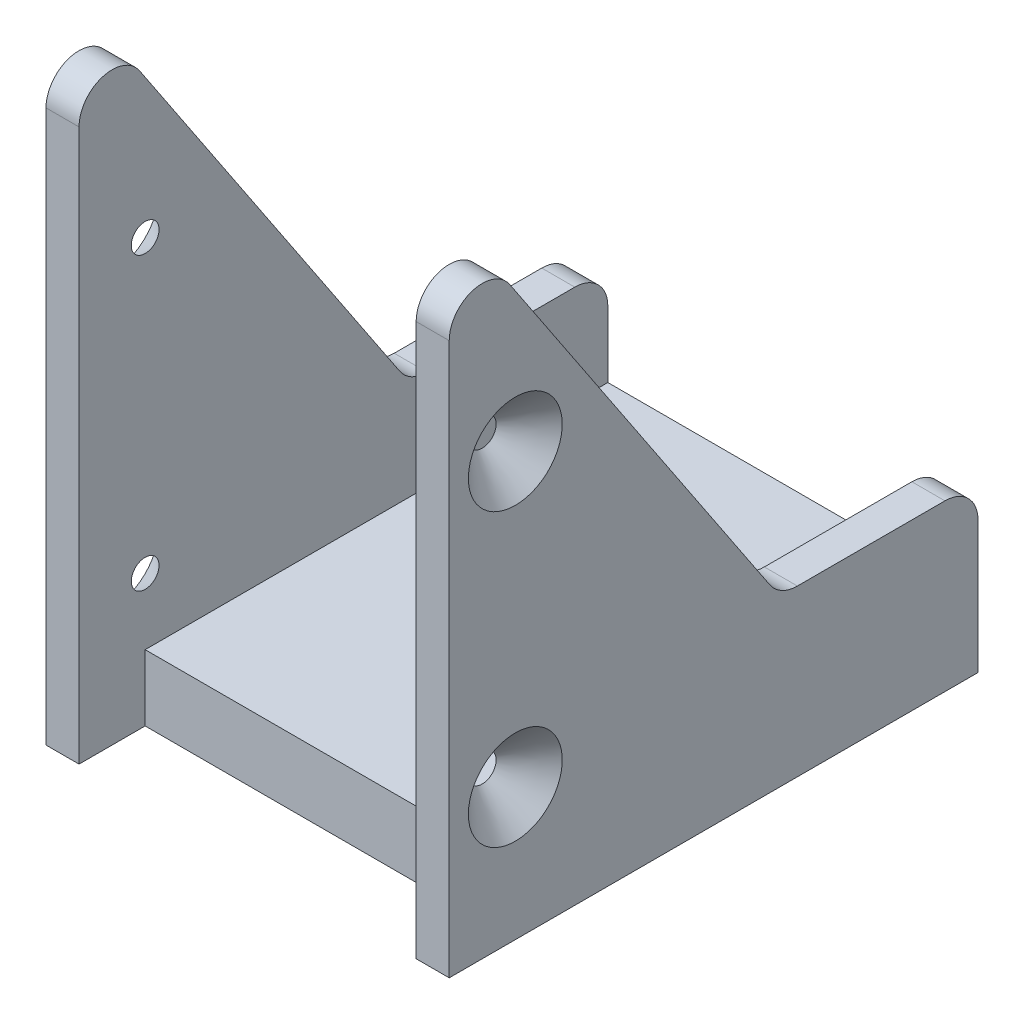
SolidWorks part; units mm, degrees
material "ABS"
ref_plane "Front Plane" through (0, 0, 0) normal (0, 0, 1) x (1, 0, 0)
ref_plane "Top Plane" through (0, 0, 0) normal (0, 1, 0) x (1, 0, 0)
ref_plane "Right Plane" through (0, 0, 0) normal (1, 0, 0) x (0, 0, -1)
sketch "Sketch1" plane through (0, 0, 0) normal (0, 0, 1) x (1, 0, 0)
  line L1 (-30.5, 50) -> (30.5, 50)
  line L2 (-30.5, 50) -> (-30.5, -50)
  line L3 (-30.5, -50) -> (30.5, -50)
  line L4 (30.5, 50) -> (30.5, -50)
  line L5 (-30.5, 50) -> (30.5, -50) construction
  line L6 (-30.5, -50) -> (30.5, 50) construction
  point P0 (0, 0)
  dimension "D1" = 61
  dimension "D2" = 100
extrude "Boss-Extrude1" add sketch "Sketch1" against normal blind 80
sketch "Sketch2" plane through (-30.5, 0, 0) normal (-1, 0, 0) x (0, 0, 1)
  line L0 (-80, -25) -> (-50, -25)
  line L1 (-80, 50) -> (-80, -50) construction
  line L2 (-50, -25) -> (0, 50)
  line L3 (-80, -25) -> (-80, -50)
  line L4 (-80, -50) -> (0, -50)
  line L5 (0, -50) -> (0, 50)
  dimension "D1" = 30
  dimension "D2" = 25
extrude "Cut-Extrude1" cut sketch "Sketch2" against normal through all flip side to cut
sketch "Sketch3" plane through (0, 0, 0) normal (0, 0, 1) x (1, 0, 0)
  line L0 (-25.5, 50) -> (-25.5, -40)
  line L1 (30.5, 50) -> (-30.5, 50) construction
  line L2 (-25.5, -40) -> (25.5, -40)
  line L3 (25.5, -40) -> (25.5, 50)
  line L4 (25.5, 50) -> (-25.5, 50)
  line L5 (0, 50) -> (0, -40) construction
  line L6 (-30.5, 50) -> (-30.5, -50) construction
  line L8 (-30.5, -50) -> (30.5, -50) construction
  dimension "D1" = 5
  dimension "D2" = 10
extrude "Cut-Extrude2" cut sketch "Sketch3" against normal through all
sketch "Sketch4" plane through (0, -40, 0) normal (0, 1, 0) x (1, 0, 0)
  line L0 (-25.5, 0) -> (25.5, 0)
  line L1 (25.5, 0) -> (25.5, 10)
  line L2 (25.5, 80) -> (25.5, 0) construction
  line L3 (25.5, 10) -> (-25.5, 10)
  line L4 (-25.5, 80) -> (-25.5, 0) construction
  line L5 (-25.5, 10) -> (-25.5, 0)
  dimension "D1" = 10
extrude "Cut-Extrude3" cut sketch "Sketch4" against normal through all
sketch "Sketch5" plane through (0, -40, 0) normal (0, 1, 0) x (1, 0, 0)
  line L0 (0, 10) -> (0, 80) construction
  line L1 (25.5, 10) -> (-25.5, 10) construction
  line L2 (-25.5, 80) -> (25.5, 80) construction
  line L3 (25.5, 55) -> (-25.5, 55) construction
  line L4 (25.5, 80) -> (25.5, 10) construction
  line L5 (-25.5, 80) -> (-25.5, 10) construction
  circle A2 centre (0, 55) radius 3.5
  dimension "D1" = 25
  dimension "D2" = 7
sketch "Sketch6" plane through (-30.5, 0, 0) normal (-1, 0, 0) x (0, 0, 1)
  line L0 (-10, 35) -> (-10, -50) construction
  line L1 (0, 50) -> (-50, -25) construction
  line L2 (-80, -50) -> (0, -50) construction
  line L3 (0, 50) -> (0, -50) construction
  point P9 (-10, 14)
  point P10 (-10, -8)
  point P11 (-10, -30)
  dimension "D1" = 10
  dimension "D3" = 22
  dimension "D4" = 22
  dimension "D5" = 20
ref_plane "Plane1" through (0, 0, -10) normal (0, 0, 1) x (1, 0, 0)
sketch "Sketch9" plane through (0, 0, -10) normal (0, 0, 1) x (1, 0, 0)
  line L0 (-30.5, -30) -> (-23.4, -30) construction
  line L1 (-30.5, -8) -> (-23.4, -8) construction
  line L2 (-30.5, 14) -> (-23.4, 14) construction
  line L3 (-23.4, -30) -> (-30.5, -37.1)
  line L4 (-30.5, -37.1) -> (-30.5, -30)
  line L5 (-30.5, -30) -> (-23.4, -30)
  line L6 (-23.4, -8) -> (-30.5, -15.1)
  line L7 (-30.5, -15.1) -> (-30.5, -8)
  line L8 (-30.5, -8) -> (-23.4, -8)
  line L9 (-23.4, 14) -> (-30.5, 6.9)
  line L10 (-30.5, 6.9) -> (-30.5, 14)
  line L11 (-25.5, 50) -> (-25.5, -50) construction
  line L12 (-25.5, 50) -> (-25.5, -50) construction
  line L13 (-23.4, 14) -> (-30.5, 14)
  point P14 (-25.5, -32.1)
  point P15 (-25.5, -10.1)
  point P16 (-25.5, 11.9)
  dimension "D1" = 2.1
  dimension "D2" = 45
  dimension "D3" = 2.1
  dimension "D4" = 2.1
ref_axis "Axis1" through (-30.5, -30, -10) along (1, 0, 0)
ref_axis "Axis2" through (-30.5, -8, -10) along (1, 0, 0)
ref_axis "Axis3" through (-30.5, 14, -10) along (1, 0, 0)
revolve "Cut-Revolve2" [suppressed] cut sketch "Sketch9" angle 360 about axis through (-30.5, -8, -10) along (1, 0, 0)
revolve "Cut-Revolve4" cut sketch "Sketch9<8>" angle 360 about axis through (-30.5, 14, -10) along (1, 0, 0)
sketch "Sketch9<8>" plane through (0, 0, -10) normal (0, 0, 1) x (1, 0, 0) same geometry as "Sketch9"
revolve "Cut-Revolve5" cut sketch "Sketch9<9>" angle 360 about axis through (-30.5, -30, -10) along (1, 0, 0)
sketch "Sketch9<9>" plane through (0, 0, -10) normal (0, 0, 1) x (1, 0, 0) same geometry as "Sketch9"
mirror "Mirror1" about plane through (0, 0, 0) normal (1, 0, 0) of "Cut-Revolve4", "Cut-Revolve5", "Cut-Revolve2"
fillet "Fillet3" radius 5 2 edges at (28, 50, 0) (-28, 50, 0)
fillet "Fillet4" radius 5 4 edges at (28, -25, -80) (-28, -25, -80) (-28, -25, -50) (28, -25, -50)
extrude "Cut-Extrude4" cut sketch "Sketch5" against normal through all contours A2
